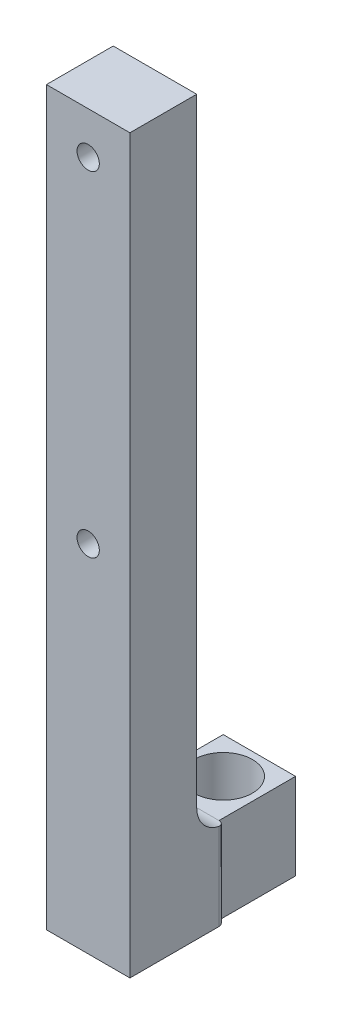
SolidWorks part; units mm, degrees
ref_plane "Front Plane" through (0, 0, 0) normal (0, 0, 1) x (1, 0, 0)
ref_plane "Top Plane" through (0, 0, 0) normal (0, 1, 0) x (1, 0, 0)
ref_plane "Right Plane" through (0, 0, 0) normal (1, 0, 0) x (0, 0, -1)
sketch "Sketch1" plane through (0, 0, 0) normal (0, 1, 0) x (1, 0, 0)
  line L0 (-3.25, -3.25) -> (3.25, -3.25)
  line L1 (-3.25, -3.25) -> (-3.25, 3.25)
  line L2 (3.25, -3.25) -> (3.25, 3.25)
  line L3 (-3.25, 3.25) -> (3.25, 3.25)
  line L4 (-3.25, -3.25) -> (3.25, 3.25) construction
  line L5 (3.25, -3.25) -> (-3.25, 3.25) construction
  circle A0 centre (0, 0) radius 2.625
  point P1 (0, 0)
  dimension "D3" = 5.25
  dimension "D1" = 6.5
  dimension "D2" = 6.5
extrude "Boss-Extrude1" add sketch "Sketch1" along normal blind 7.75
sketch "Sketch2" plane through (0, 0, 3.25) normal (0, 0, 1) x (1, 0, 0)
  line L1 (3.25, 0) -> (-3.25, 0)
  line L2 (3.25, 0) -> (3.25, 7.75)
  line L3 (3.25, 7.75) -> (-3.25, 7.75)
  line L4 (-3.25, 0) -> (-3.25, 7.75)
extrude "Boss-Extrude2" add sketch "Sketch2" along normal blind 8.88
sketch "Sketch3" plane through (0, 7.75, 0) normal (0, 1, 0) x (1, 0, 0)
  line L0 (-3.25, 3.25) -> (-3.25, -12.13) construction
  line L1 (3.25, -12.13) -> (-3.25, -12.13)
  line L2 (3.25, -12.13) -> (3.25, -6.13)
  line L3 (3.25, -6.13) -> (-3.25, -6.13)
  line L4 (-3.25, -12.13) -> (-3.25, -6.13)
  dimension "D1" = 6
extrude "Boss-Extrude3" add sketch "Sketch3" along normal blind 58.01
fillet "Fillet1" radius 2.5 1 edges at (0, 7.75, 6.13) type face fillet first side face at (0, 7.75, 2.625) second side face at (0, 36.755, 6.13)
sketch "Sketch4" plane through (3.25, 0, 0) normal (1, 0, 0) x (0, 0, -1)
  line L0 (-3.63, 7.75) -> (-3.63, 0)
  line L1 (-12.13, 0) -> (3.25, 0) construction
  line L2 (-3.63, 0) -> (-12.13, 0)
  line L3 (-12.13, 0) -> (-12.13, 65.76)
  line L4 (-12.13, 65.76) -> (-6.13, 65.76)
  line L5 (-6.13, 65.76) -> (-6.13, 10.25)
  arc A0 (-6.13, 10.25) -> (-3.63, 7.75) centre (-3.63, 10.25) ccw
extrude "Boss-Extrude4" add sketch "Sketch4" along normal blind 0.5
fillet "Fillet2" radius 0.5 1 edges at (3.75, 3.875, 3.63) type face fillet first side face at (3.5, 3.875, 3.63) second side face at (3.75, 24.8337, 7.383)
mirror "Mirror1" about plane through (0, 0, 0) normal (1, 0, 0) of "Boss-Extrude4"
fillet "Fillet3" radius 0.5 1 edges at (-3.75, 3.875, 3.63) type face fillet first side face at (-3.5, 3.875, 3.63) second side face at (-3.75, 24.8337, 7.383)
sketch "Sketch6" plane through (0, 0, 6.13) normal (0, 0, -1) x (-1, 0, 0)
  line L0 (0, 65.76) -> (0, 61.975)
  line L1 (-3.75, 65.76) -> (3.75, 65.76) construction
  line L3 (2.25, 61.975) -> (1.125, 63.9236)
  line L4 (1.125, 63.9236) -> (-1.125, 63.9236)
  line L5 (-1.125, 63.9236) -> (-2.25, 61.975)
  line L6 (-2.25, 61.975) -> (-1.125, 60.0264)
  line L7 (-1.125, 60.0264) -> (1.125, 60.0264)
  line L8 (1.125, 60.0264) -> (2.25, 61.975)
  circle A0 centre (0, 61.975) radius 1
  circle A1 centre (0, 61.975) radius 2.25
  circle A2 centre (0, 61.975) radius 1.9486 construction
  dimension "D2" = 2
  dimension "D3" = 4.5
  dimension "D1" = 3.785
extrude "Cut-Extrude3" cut sketch "Sketch6" against normal through all contours A0 region at (-0.6871, 62.6621, 6.13)
extrude "Cut-Extrude4" cut sketch "Sketch6<3>" against normal blind 2 contours A0 L4 L5 L6 L7 L8 L3 region at (-0.5625, 63.864, 6.13)
sketch "Sketch6<3>" plane through (0, 0, 6.13) normal (0, 0, -1) x (-1, 0, 0) same geometry as "Sketch6"
ref_plane "Plane1" through (0, 46.94, 0) normal (0, 1, 0) x (1, 0, 0)
mirror "Mirror2" about plane through (0, 46.94, 0) normal (0, 1, 0) of "Cut-Extrude4", "Cut-Extrude3"
